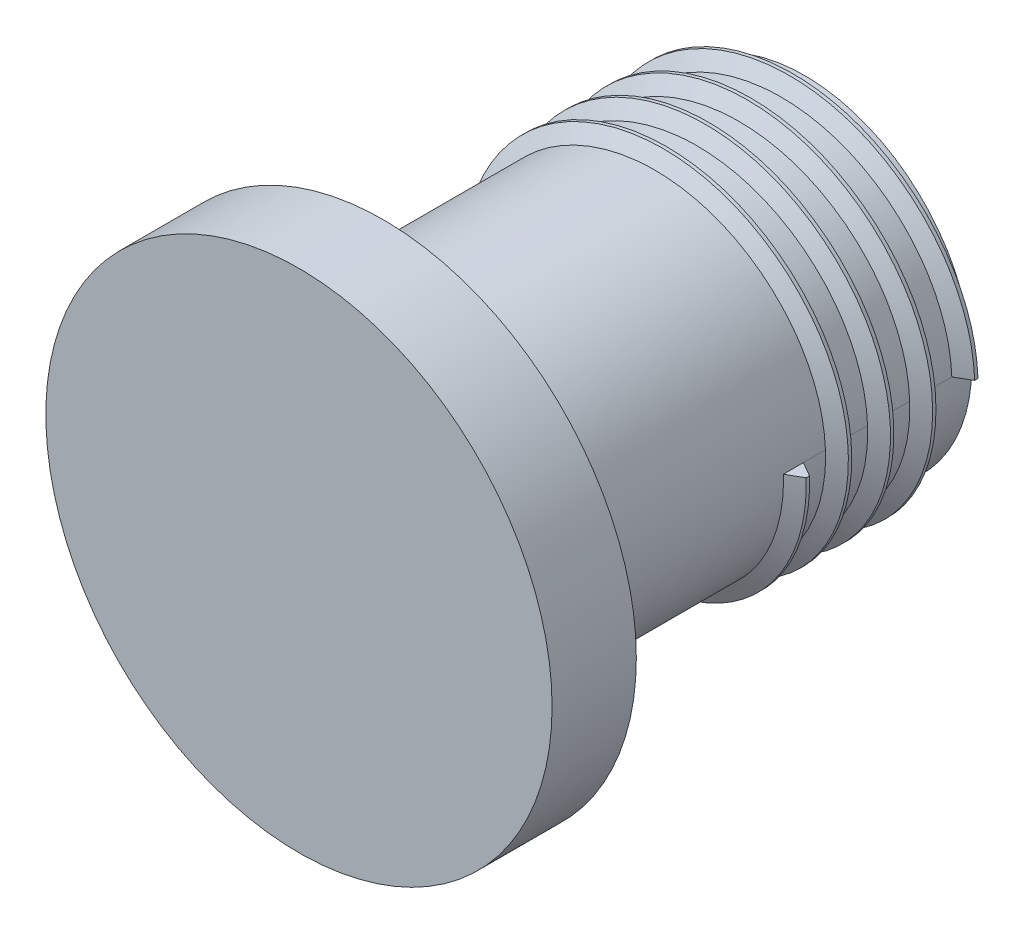
SolidWorks part; units mm, degrees
ref_plane "前基準面" through (0, 0, 0) normal (0, 0, 1) x (1, 0, 0)
ref_plane "上基準面" through (0, 0, 0) normal (0, 1, 0) x (1, 0, 0)
ref_plane "右基準面" through (0, 0, 0) normal (1, 0, 0) x (0, 0, -1)
sketch "草圖1" plane through (0, 0, 0) normal (0, 0, 1) x (1, 0, 0)
  circle A0 centre (0, 0) radius 3.0043
extrude "填料-伸長1" add sketch "草圖1" along normal blind 1
sketch "草圖2" plane through (0, 0, 0) normal (0, 0, -1) x (-1, 0, 0)
  circle A0 centre (0, 0) radius 1.9868
extrude "填料-伸長2" add sketch "草圖2" along normal blind 5
thread "螺紋2" pitch 0.3175 method extrude profile "螺紋輪廓4" start angle 0, offset 0, length 2, pitch 0.5, diameter 3.9736
ref_plane "平面4" through (1.9868, 0, -5) normal (0, -1, 0) x (1, 0, 0)
sketch "螺紋輪廓4" plane through (1.9868, 0, -5) normal (0, -1, 0) x (1, 0, 0)
  line L0 (0, 0) -> (0, 0.3175) construction
  line L1 (0, 0) -> (0.1719, 0.0992)
  line L2 (0.1719, 0.0992) -> (0.1719, 0.1389)
  line L3 (0.1719, 0.1389) -> (0, 0.2381)
  line L4 (0.1719, 0.1191) -> (0, 0.1191) construction
  line L11 (0, 0) -> (0, 0.2381)
  point P2 (0, 0)
  dimension "Pitch" = 0.3175
  dimension "Profile_Angle" = 60
  dimension "Profile_Land" = 0.0397
  dimension "Profile_Height" = 0.1719
